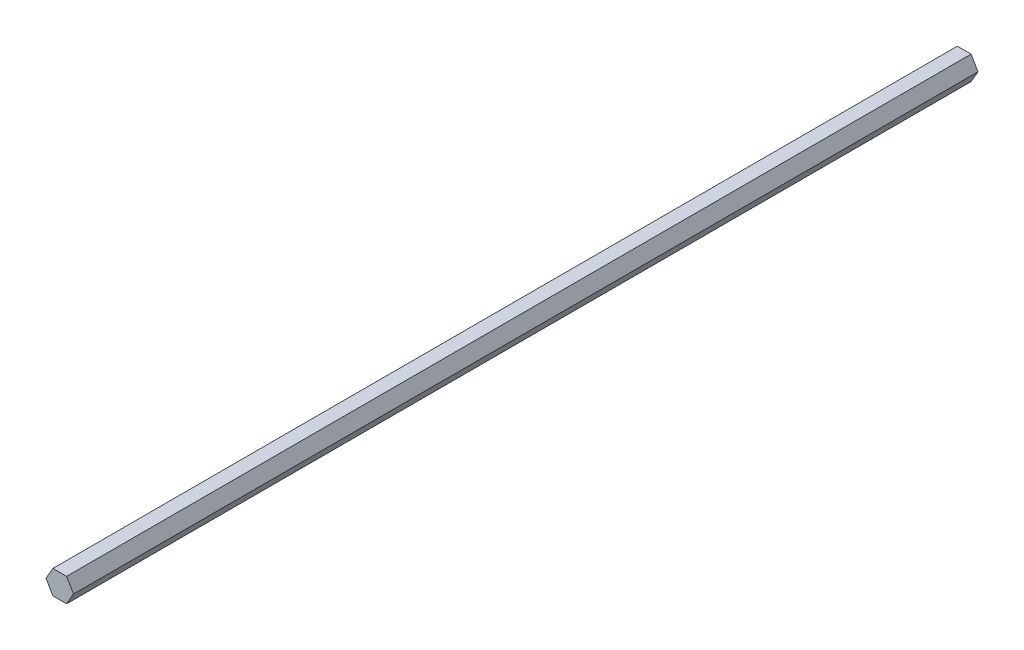
SolidWorks part; units mm, degrees
ref_plane "Front Plane" through (0, 0, 0) normal (0, 0, 1) x (1, 0, 0)
ref_plane "Top Plane" through (0, 0, 0) normal (0, 1, 0) x (1, 0, 0)
ref_plane "Right Plane" through (0, 0, 0) normal (1, 0, 0) x (0, 0, -1)
sketch "Sketch2" plane through (0, 0, 0) normal (0, 0, 1) x (1, 0, 0)
  line L1 (3.6662, -6.35) -> (7.3323, 0)
  line L2 (7.3323, 0) -> (3.6662, 6.35)
  line L3 (3.6662, 6.35) -> (-3.6662, 6.35)
  line L4 (-3.6662, 6.35) -> (-7.3323, 0)
  line L5 (-7.3323, 0) -> (-3.6662, -6.35)
  line L6 (-3.6662, -6.35) -> (3.6662, -6.35)
  circle A0 centre (0, 0) radius 6.35 construction
  dimension "D1" = 12.7
extrude "Boss-Extrude1" add sketch "Sketch2" along normal mid plane 482.6
ref_axis "Axis1" through (0, 0, 349.25) along (0, 0, -1)
